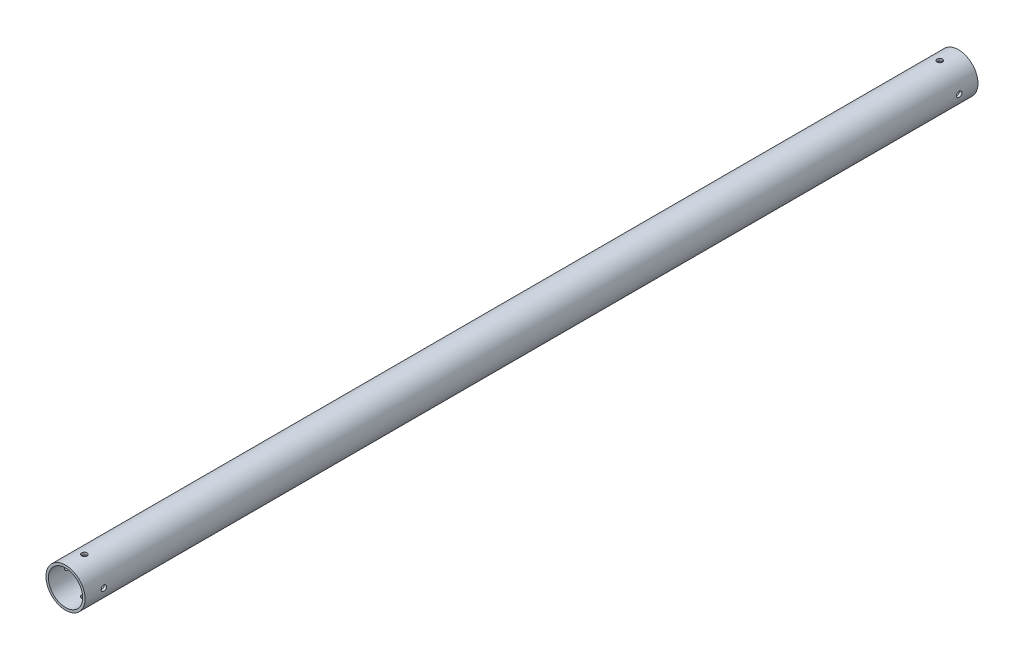
SolidWorks part; units mm, degrees
material "PC High Viscosity"
ref_plane "Front Plane" through (0, 0, 0) normal (0, 0, 1) x (1, 0, 0)
ref_plane "Top Plane" through (0, 0, 0) normal (0, 1, 0) x (1, 0, 0)
ref_plane "Right Plane" through (0, 0, 0) normal (1, 0, 0) x (0, 0, -1)
sketch "Sketch2" plane through (0, 0, 0) normal (0, 0, 1) x (1, 0, 0)
  circle A0 centre (0, 0) radius 11.1125
  circle A1 centre (0, 0) radius 12.7
  dimension "D1" = 25.4
  dimension "D2" = 1.5875
extrude "Boss-Extrude1" add sketch "Sketch2" along normal mid plane 579.1873
sketch "Sketch3" plane through (0, 0, 0) normal (0, 1, 0) x (1, 0, 0)
  line L0 (12.7, 289.5936) -> (-12.7, 289.5936) construction
  line L1 (-13.97, 0) -> (13.97, 0) construction
  circle A0 centre (0, 277.4016) radius 1.7526
  circle A1 centre (0, -277.4016) radius 1.7526
  dimension "D1" = 3.5052
  dimension "D2" = 12.192
extrude "Cut-Extrude1" cut sketch "Sketch3" against normal through all both and the other way through all
sketch "Sketch5" plane through (0, 0, 0) normal (1, 0, 0) x (0, 0, -1)
  line L0 (289.5936, -12.7) -> (289.5936, 12.7) construction
  line L1 (0, 13.97) -> (0, -13.97) construction
  circle A0 centre (277.4016, 0) radius 1.7526
  circle A1 centre (-277.4016, 0) radius 1.7526
  dimension "D1" = 3.5052
  dimension "D2" = 12.192
extrude "Cut-Extrude2" cut sketch "Sketch5" against normal through all both and the other way through all
